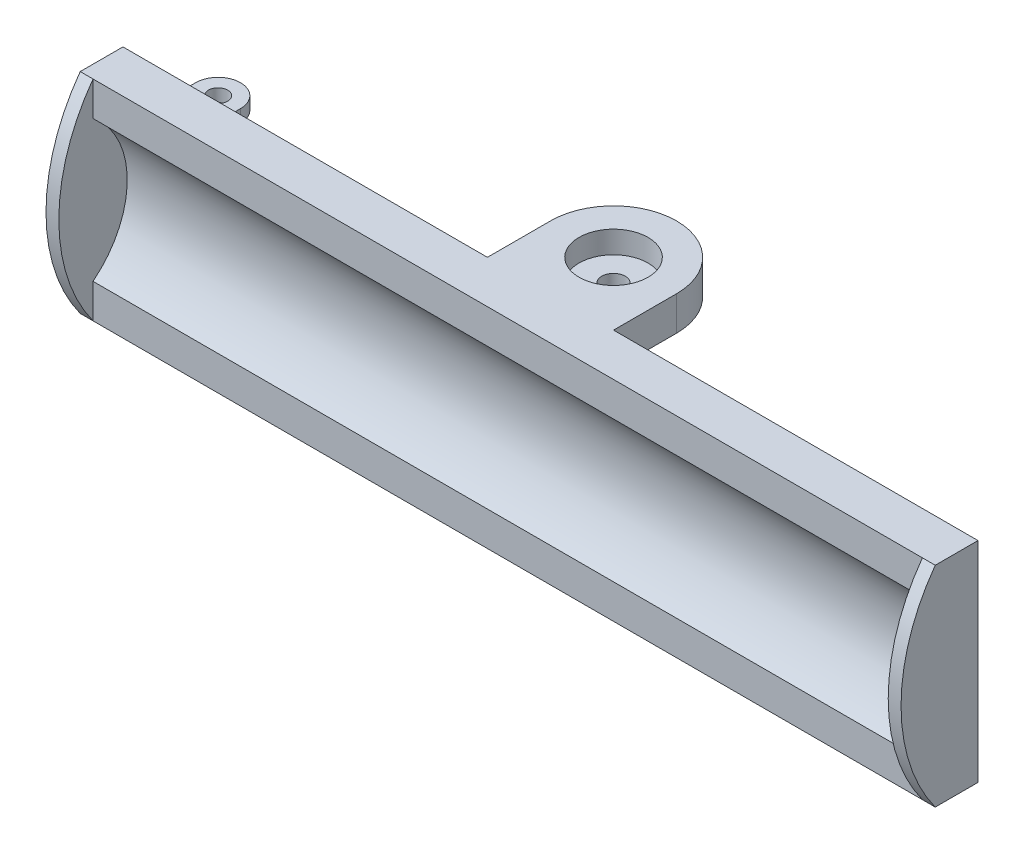
SolidWorks part; units mm, degrees
ref_plane "Front Plane" through (0, 0, 0) normal (1, 0, 0) x (0, 1, 0)
ref_plane "Top Plane" through (0, 0, 0) normal (0, 0, 1) x (0, 1, 0)
ref_plane "Right Plane" through (0, 0, 0) normal (0, 1, 0) x (-1, 0, 0)
sketch "Sketch1" plane through (0, 0, 0) normal (1, 0, 0) x (0, 1, 0)
  line L0 (-5.9881, -2) -> (7.7891, -2) construction
  line L1 (-24.5, -5) -> (24.5, -5)
  line L2 (-24.5, -5) -> (-24.5, 5)
  line L3 (-24.5, 5) -> (24.5, 5)
  line L4 (24.5, -5) -> (24.5, 5)
  line L5 (-24.5, -5) -> (24.5, 5) construction
  line L6 (-24.5, 5) -> (24.5, -5) construction
  circle A0 centre (0, 18) radius 20 construction
  circle A1 centre (0, 18) radius 21
  point P0 (0, 0)
  dimension "D3" = 40
  dimension "D4" = 3
  dimension "D1" = 49
  dimension "D2" = 10
  dimension "D5" = 1
extrude "Boss-Extrude1" add sketch "Sketch1" along normal mid plane 200 contours A1 L3 L2 L1 L4 region at (0, -23.9999, 0)
ref_plane "Midplane Width" through (0, 0, 0) normal (0, -1, 0) x (-1, 0, 0)
sketch "Sketch3" plane through (0, -24.5, 0) normal (0, -1, 0) x (1, 0, 0)
  line L0 (100, -5) -> (-100, -5) construction
  line L1 (-14.75, -19.75) -> (-14.75, -5)
  line L2 (14.75, -19.75) -> (14.75, -5)
  line L3 (-14.75, -5) -> (14.75, -5)
  circle A0 centre (0, -19.75) radius 2.75
  circle A1 centre (0, -19.75) radius 14.75
  line M4 (-100, -5) -> (100, -5)
  dimension "D2" = 12
extrude "Boss-Extrude2" add sketch "Sketch3" against normal blind 8 contours A1 A0 | A1 L1 M4 | A1 L2 L3 region at (-10.1348, -24.5, -9.6152) region at (-11.4553, -24.5, -8.2947) region at (11.4553, -24.5, -8.2947)
sketch "Sketch4" plane through (0, -24.5, 0) normal (0, -1, 0) x (-1, 0, 0)
  circle A0 centre (0, 19.75) radius 8.075
  dimension "D1" = 16.15
extrude "Cut-Extrude1" cut sketch "Sketch4" against normal blind 5.2
sketch "Sketch5" plane through (0, -16.5, 0) normal (0, 1, 0) x (-1, 0, 0)
  circle A0 centre (0, -19.75) radius 2.745
  circle A1 centre (0, -19.75) radius 2.75 construction
  circle A2 centre (0, -19.75) radius 2.75
  dimension "D1" = 5.49
mirror "Mirror1" about plane through (0, 0, 0) normal (0, -1, 0) of "Boss-Extrude2", "Cut-Extrude1"
sketch "Sketch6" plane through (0, 0, 0) normal (0, -1, 0) x (-1, 0, 0)
  line L0 (0, 19.75) -> (92.5, 19.75)
  line L1 (87.25, 19.75) -> (87.25, 5)
  line L2 (14.75, 5) -> (100, 5) construction
  line L3 (97.75, 19.75) -> (97.75, 5)
  line L4 (97.75, 5) -> (87.25, 5)
  circle A0 centre (92.5, 19.75) radius 2.25
  arc A1 (97.75, 19.75) -> (87.25, 19.75) centre (92.5, 19.75) ccw
  circle A2 centre (92.5, 19.75) radius 5.25 construction
  circle A3 centre (0, 19.75) radius 2.745 construction
  circle A4 centre (0, 19.75) radius 2.745
  dimension "D2" = 4.5
  dimension "D1" = 92.5
  dimension "D3" = 3
extrude "Boss-Extrude5" add sketch "Sketch6" along normal blind 3 from offset 8 contours L3 A1 A0 L1 L4 region at (-92.5, 0, -14.0126)
mirror "Mirror2" about plane through (0, 0, 0) normal (0, -1, 0) of "Boss-Extrude5"
sketch "Sketch7" plane through (-100, 0, 0) normal (-1, 0, 0) x (0, -1, 0)
  line L0 (0, 13) -> (-33.9955, 13) construction
  line L1 (-16.4924, 5) -> (16.4924, 5)
  line L5 (-16.4924, 5) -> (-24.5, 5)
  line L6 (-24.5, 5) -> (-24.5, -5)
  line L7 (-24.5, -5) -> (24.5, -5)
  line L8 (24.5, -5) -> (24.5, 5)
  line L9 (24.5, 5) -> (16.4924, 5)
  line L10 (-16.4924, 5) -> (-24.5, 5)
  line L11 (-24.5, 5) -> (-24.5, -5)
  line L12 (-24.5, -5) -> (24.5, -5)
  line L13 (24.5, -5) -> (24.5, 5)
  line L14 (24.5, 5) -> (16.4924, 5)
  arc A0 (24.5, 5) -> (-24.5, 5) centre (0, -28.5156) ccw
  arc A1 (-16.4924, 5) -> (16.4924, 5) centre (0, 18) ccw
  arc A2 (-16.4924, 5) -> (16.4924, 5) centre (0, 18) ccw
  arc M9 (16.4924, 5) -> (-16.4924, 5) centre (0, 18) cw
  line M10 (-16.4924, 5) -> (-24.5, 5)
  line M11 (-24.5, 5) -> (-24.5, -5)
  line M12 (-24.5, -5) -> (24.5, -5)
  line M13 (24.5, -5) -> (24.5, 5)
  line M14 (24.5, 5) -> (16.4924, 5)
  dimension "D2" = 8
  dimension "D1" = 0
extrude "Boss-Extrude6" add sketch "Sketch7" against normal blind 3 contours M14 M9 M10 M11 M12 M13 | L1 M9 | A0 L1 M14 M10 region at (-100, 0, 8.228) region at (-100, 0, -3.5001) region at (-100, 0, 1.7412)
mirror "Mirror3" about plane through (0, 0, 0) normal (1, 0, 0) of "Boss-Extrude6"
